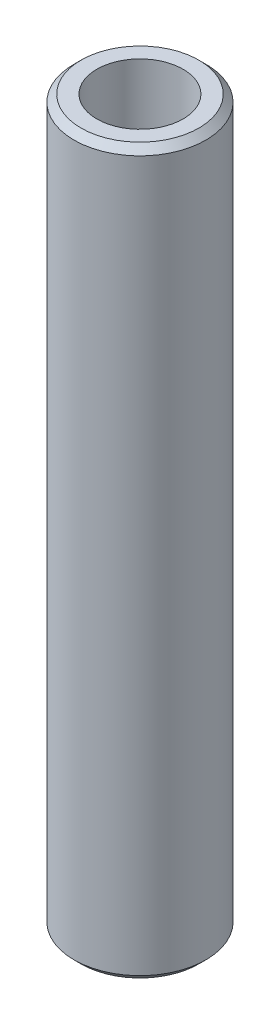
SolidWorks part; units mm, degrees
ref_plane "Front Plane" through (0, 0, 0) normal (0, 0, 1) x (1, 0, 0)
ref_plane "Top Plane" through (0, 0, 0) normal (0, 1, 0) x (1, 0, 0)
ref_plane "Right Plane" through (0, 0, 0) normal (1, 0, 0) x (0, 0, -1)
sketch "Sketch1" plane through (0, 0, 0) normal (0, 1, 0) x (1, 0, 0)
  circle A0 centre (0, 0) radius 12.5
  dimension "SHAFT_OD" = 25
extrude "Boss-Extrude1" add sketch "Sketch1" along normal blind 137.3903
sketch "Sketch2" plane through (0, 0, 0) normal (0, 1, 0) x (1, 0, 0)
  circle A0 centre (0, 0) radius 8.1859
  dimension "BORE_D" = 16.3717
extrude "Cut-Extrude1" cut sketch "Sketch2" along normal through all
chamfer "Chamfer1" distance 1.3201 angle 45 2 edges at (0, 137.3903, 12.5) (0, 0, 12.5)
